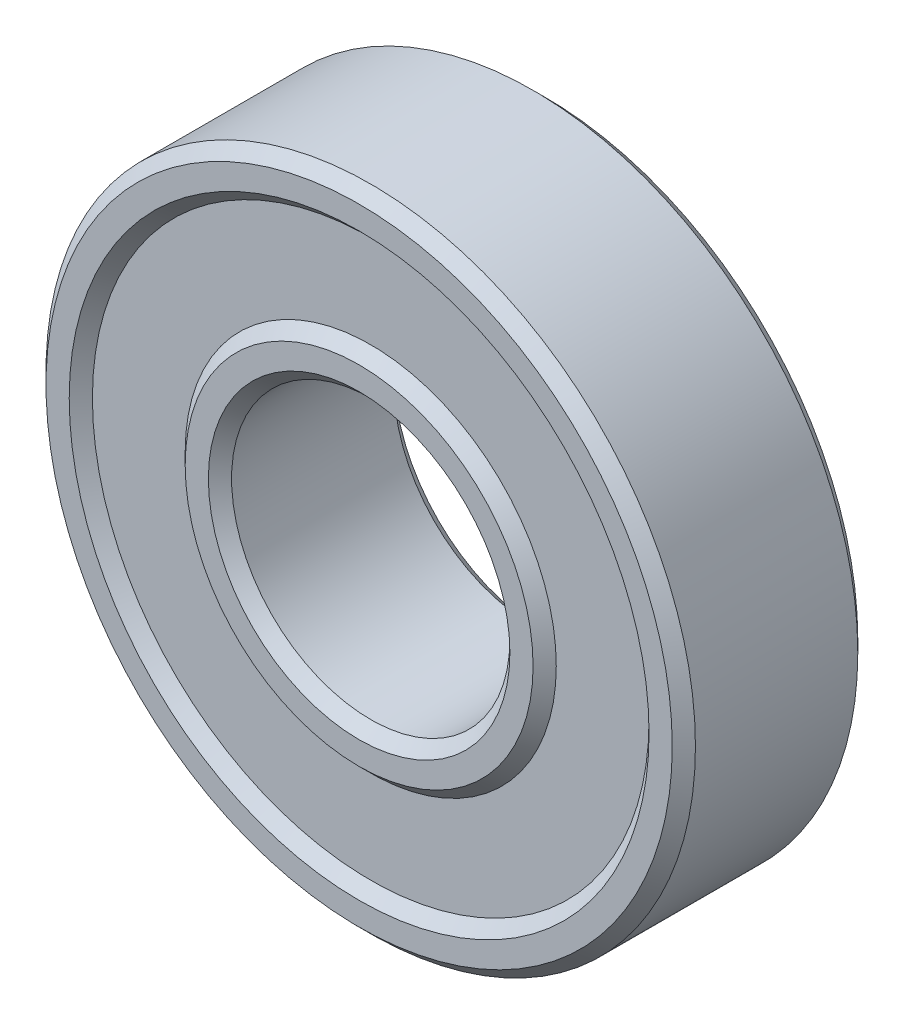
SolidWorks part; units mm, degrees
ref_plane "Front Plane" through (0, 0, 0) normal (0, 0, 1) x (1, 0, 0)
ref_plane "Top Plane" through (0, 0, 0) normal (0, 1, 0) x (1, 0, 0)
ref_plane "Right Plane" through (0, 0, 0) normal (1, 0, 0) x (0, 0, -1)
sketch "Sketch1" plane through (0, 0, 0) normal (0, 0, 1) x (1, 0, 0)
  circle A0 centre (0, 0) radius 14
  circle A1 centre (0, 0) radius 6
  circle A2 centre (0, 0) radius 12
  circle A3 centre (0, 0) radius 8
  dimension "D1" = 12
  dimension "D2" = 28
  dimension "D3" = 2
  dimension "D4" = 2
extrude "Boss-Extrude1" add sketch "Sketch1" along normal mid plane 8 contours A0 | A1
extrude "Cut-Extrude1" cut sketch "Sketch1<3>" along normal blind 0.5 from surface contours A2 A3 region at (-11.6606, 0, 0) starting at face at (14, 0, -4)
sketch "Sketch1<3>" plane through (0, 0, 0) normal (0, 0, 1) x (1, 0, 0) same geometry as "Sketch1"
extrude "Cut-Extrude2" cut sketch "Sketch1<4>" against normal blind 0.5 from surface contours A2 A3 region at (-11.6606, 0, 0) starting at face at (14, 0, 4)
sketch "Sketch1<4>" plane through (0, 0, 0) normal (0, 0, 1) x (1, 0, 0) same geometry as "Sketch1"
chamfer "Chamfer1" distance 0.5 angle 45 8 edges at (12, 0, -4) (6, 0, -4) (8, 0, -4) (8, 0, 4) (6, 0, 4) (12, 0, 4) (14, 0, -4) (14, 0, 4)
